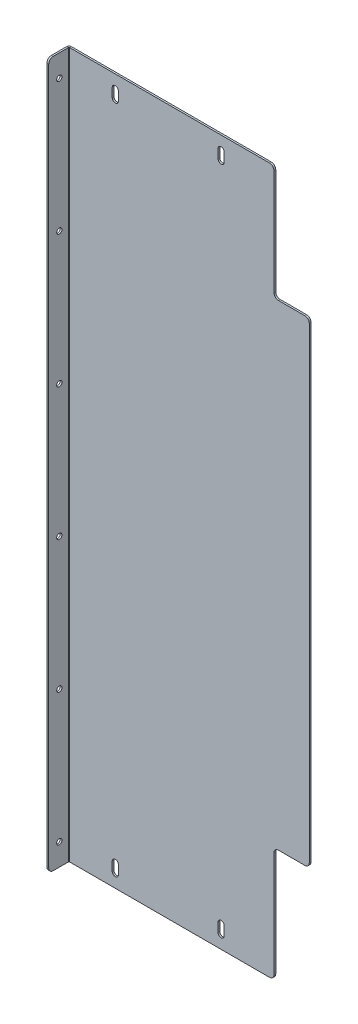
SolidWorks part; units mm, degrees
note: The reader was unsure of these and kept them because the rebuilt part matched: flange length of "边线-法兰1".
ref_plane "前视基准面" through (0, 0, 0) normal (0, 0, 1) x (1, 0, 0)
ref_plane "上视基准面" through (0, 0, 0) normal (0, 1, 0) x (1, 0, 0)
ref_plane "右视基准面" through (0, 0, 0) normal (1, 0, 0) x (0, 0, -1)
sketch "草图1" plane through (0, 0, 0) normal (0, 0, 1) x (1, 0, 0)
  line L1 (275, -400) -> (-275, -400)
  line L2 (275, -400) -> (275, 400)
  line L3 (275, 400) -> (-275, 400)
  line L4 (-275, -400) -> (-275, 400)
  line L5 (275, -400) -> (-275, 400) construction
  line L6 (275, 400) -> (-275, -400) construction
  point P0 (0, 0)
  dimension "D1" = 550
  dimension "D2" = 800
base flange "基体-法兰1" sketch "草图1" thickness 2 reverse thickness direction no parameters "D1"=0.7366
sketch "草图6" plane through (0, 0, 0) normal (0, 0, 1) x (1, 0, 0)
  line L1 (275, 400) -> (235, 400)
  line L2 (275, 400) -> (275, 270)
  line L3 (275, 270) -> (235, 270)
  line L4 (235, 400) -> (235, 270)
  line L5 (275, -400) -> (235, -400)
  line L6 (275, -400) -> (275, -270)
  line L7 (275, -270) -> (235, -270)
  line L8 (235, -400) -> (235, -270)
  dimension "D1" = 40
  dimension "D2" = 40
  dimension "D3" = 130
  dimension "D4" = 130
extrude "切除-拉伸1" cut sketch "草图6" against normal blind 10 normal cut yes
fillet "圆角1" radius 5 8 edges at (235, -270, -1) (235, 270, -1) (-275, -400, -1) (235, -400, -1) (275, -270, -1) (275, 270, -1) (235, 400, -1) (-275, 400, -1)
sketch "草图7" plane through (0, 0, 0) normal (0, 0, 1) x (1, 0, 0)
  line L1 (0.5, -422.7528) -> (-0.5, -422.7528)
  line L2 (0.5, -422.7528) -> (0.5, 422.7528)
  line L3 (0.5, 422.7528) -> (-0.5, 422.7528)
  line L4 (-0.5, -422.7528) -> (-0.5, 422.7528)
  line L5 (0.5, -422.7528) -> (-0.5, 422.7528) construction
  line L6 (0.5, 422.7528) -> (-0.5, -422.7528) construction
  point P0 (0, 0)
  dimension "D1" = 1
extrude "切除-拉伸2" cut sketch "草图7" against normal blind 10 normal cut yes
sketch "草图8" plane through (0, 0, 0) normal (0, 0, 1) x (1, 0, 0)
  line L1 (-0.5, 400) -> (-316.9317, 400)
  line L2 (-0.5, 400) -> (-0.5, -407.8634)
  line L3 (-0.5, -407.8634) -> (-316.9317, -407.8634)
  line L4 (-316.9317, 400) -> (-316.9317, -407.8634)
extrude "切除-拉伸3" cut sketch "草图8" against normal blind 10
edge flange "边线-法兰1" sketch "草图11" flange angle 90 flange length 25 flange position material inside bend radius 0.7366 thickness 2 relief rectangular parameters "D6"=10
sketch "草图11" plane through (0.5, 0, 0) normal (-1, 0, 0) x (0, -1, 0)
  line L2 (-400, 0) -> (-400, 23)
  line L3 (-400, 23) -> (400, 23)
  line L4 (400, 23) -> (400, 0)
  line L7 (400, 0) -> (-400, 0) construction
  line L8 (400, 0) -> (-400, 0)
bend "边线折弯1" bend radius 0.7366 bend angle 90 parameters "D5"=1
fillet "圆角2" radius 5 2 edges at (1.5, 400, 23) (1.5, -400, 23)
sketch "草图12" plane through (0, 0, 0) normal (0, 0, 1) x (1, 0, 0)
  line L0 (55, 375) -> (55, 385) construction
  line L1 (51.5, 375) -> (51.5, 385)
  line L2 (58.5, 375) -> (58.5, 385)
  line L3 (175, 375) -> (175, 385) construction
  line L4 (171.5, 375) -> (171.5, 385)
  line L5 (178.5, 375) -> (178.5, 385)
  line L6 (55, -385) -> (55, -375) construction
  line L7 (51.5, -385) -> (51.5, -375)
  line L8 (58.5, -385) -> (58.5, -375)
  line L9 (175, -385) -> (175, -375) construction
  line L10 (171.5, -385) -> (171.5, -375)
  line L11 (178.5, -385) -> (178.5, -375)
  line L12 (235, 395) -> (235, 275) construction
  arc A0 (51.5, 375) -> (58.5, 375) centre (55, 375) ccw
  arc A1 (58.5, 385) -> (51.5, 385) centre (55, 385) ccw
  arc A2 (171.5, 375) -> (178.5, 375) centre (175, 375) ccw
  arc A3 (178.5, 385) -> (171.5, 385) centre (175, 385) ccw
  arc A4 (51.5, -385) -> (58.5, -385) centre (55, -385) ccw
  arc A5 (58.5, -375) -> (51.5, -375) centre (55, -375) ccw
  arc A6 (171.5, -385) -> (178.5, -385) centre (175, -385) ccw
  arc A7 (178.5, -375) -> (171.5, -375) centre (175, -375) ccw
  point P2 (55, 380)
  point P8 (175, 380)
  point P15 (55, -380)
  point P22 (175, -380)
  dimension "D12" = 120
  dimension "D1" = 7
  dimension "D2" = 7
  dimension "D3" = 10
  dimension "D4" = 10
  dimension "D5" = 7
  dimension "D6" = 7
  dimension "D7" = 760
  dimension "D8" = 380
  dimension "D9" = 10
  dimension "D10" = 10
  dimension "D11" = 60
extrude "切除-拉伸4" cut sketch "草图12" against normal blind 10 normal cut yes
sketch "草图13" plane through (2.5, 0, 0) normal (1, 0, 0) x (0, 0, -1)
  line L0 (-0.7366, -400) -> (-18, -400) construction
  line L1 (-23, -395) -> (-23, 395) construction
  circle A0 centre (-11, -375) radius 3
  dimension "D3" = 6
  dimension "D1" = 25
  dimension "D2" = 12
extrude "切除-拉伸5" cut sketch "草图13" against normal blind 10 normal cut yes
pattern_linear "阵列(线性)1" count 6 spacing 150 along (0, 1, 0) of "切除-拉伸5"
sketch "折弯-线1" [suppressed] plane through (0, 0, 0) normal (0, 1, 0) x (1, 0, 0)
sketch "边界框1" [suppressed] plane through (0, 0, 0) normal (0, 1, 0) x (1, 0, 0)
sheet metal parameters "钣金1" thickness 2 parameters "D1"=0.7366
flat pattern "平板型式1" [suppressed]
sketch "折弯-线2" plane through (0, 0, 0) normal (0, 1, 0) x (1, 0, 0)
sketch3d "边界框2" [suppressed]
  line L0 (275, 310, 0) -> (275, -310, 0) construction
  line L1 (-275, 310, 0) -> (-275, -310, 0) construction
  line L2 (275, 310, 0) -> (-275, 310, 0) construction
  line L3 (275, -310, 0) -> (-275, -310, 0) construction
sheet metal parameters "钣金2" thickness 2 parameters "D1"=0.7366
flat pattern "平板型式1"
sketch "折弯-线2" plane through (0, 0, 0) normal (0, 1, 0) x (1, 0, 0)
sketch3d "边界框2" [suppressed]
  line L0 (275, -400, 0) -> (275, 400, 0) construction
  line L1 (-275, -400, 0) -> (-275, 400, 0) construction
  line L2 (275, -400, 0) -> (-275, -400, 0) construction
  line L3 (275, 400, 0) -> (-275, 400, 0) construction
sheet metal parameters "钣金3" thickness 2 parameters "D1"=0.7366
flat pattern "平板型式3"
sketch "折弯-线3" plane through (0, 0, 0) normal (0, 1, 0) x (1, 0, 0)
sketch3d "边界框3" [suppressed]
  line L0 (-0.5, -400, 0) -> (-0.5, 400, 0) construction
  line L1 (-275, -400, 0) -> (-275, 400, 0) construction
  line L2 (-0.5, -400, 0) -> (-275, -400, 0) construction
  line L3 (-0.5, 400, 0) -> (-275, 400, 0) construction
sheet metal parameters "钣金4" thickness 2 parameters "D1"=0.7366
flat pattern "平板型式4"
sketch "折弯-线4" plane through (0, 0, 0) normal (0, 1, 0) x (1, 0, 0)
sketch3d "边界框4" [suppressed]
  line L0 (274.9999, -400, 0) -> (275, 400, 0) construction
  line L1 (0.5, -400, 0) -> (0.5001, 400, 0) construction
  line L2 (274.9999, -400, 0) -> (0.5, -400, 0) construction
  line L3 (275, 400, 0) -> (0.5001, 400, 0) construction
sheet metal parameters "钣金5" thickness 2 parameters "D1"=0.7366
flat pattern "平板型式4"
sketch "折弯-线4" plane through (0, 0, 0) normal (0, 0, 1) x (1, 0, 0)
  line L0 (1.8727, 400) -> (1.8727, -400) construction
  line L1 (1.8727, 400) -> (1.8727, -400) construction
sketch3d "边界框4" [suppressed]
  line L0 (274.9999, -400, 0) -> (275, 400, 0) construction
  line L1 (-21.7546, -400, 0) -> (-21.7546, 400, 0) construction
  line L2 (274.9999, -400, 0) -> (-21.7546, -400, 0) construction
  line L3 (275, 400, 0) -> (-21.7546, 400, 0) construction
bend of the flat pattern "展平-<边线折弯1>1"
sheet metal parameters "钣金6" thickness 2 parameters "D1"=0.7366
flat pattern "平板型式4"
sketch "折弯-线4" plane through (0, 0, 0) normal (0, 0, 1) x (1, 0, 0)
  line L0 (1.8727, 400) -> (1.8727, -400) construction
  line L1 (1.8727, 400) -> (1.8727, -400) construction
sketch3d "边界框4" [suppressed]
  line L0 (274.9999, -400, 0) -> (275, 400, 0) construction
  line L1 (-21.7546, -400, 0) -> (-21.7546, 400, 0) construction
  line L2 (274.9999, -400, 0) -> (-21.7546, -400, 0) construction
  line L3 (275, 400, 0) -> (-21.7546, 400, 0) construction
bend of the flat pattern "展平-<边线折弯1>1"
sheet metal parameters "钣金7" thickness 2 parameters "D1"=0.7366
flat pattern "平板型式4"
sketch "折弯-线4" plane through (0, 0, 0) normal (0, 0, 1) x (1, 0, 0)
  line L0 (1.8727, 400) -> (1.8727, -400) construction
  line L1 (1.8727, 400) -> (1.8727, -400) construction
sketch3d "边界框4" [suppressed]
  line L0 (274.9999, -400, 0) -> (275, 400, 0) construction
  line L1 (-21.7546, -400, 0) -> (-21.7546, 400, 0) construction
  line L2 (274.9999, -400, 0) -> (-21.7546, -400, 0) construction
  line L3 (275, 400, 0) -> (-21.7546, 400, 0) construction
bend of the flat pattern "展平-<边线折弯1>1"
sheet metal parameters "钣金8" thickness 2 parameters "D1"=0.7366
flat pattern "平板型式4"
sketch "折弯-线4" plane through (0, 0, 0) normal (0, 0, 1) x (1, 0, 0)
  line L0 (1.8727, 400) -> (1.8727, -400) construction
  line L1 (1.8727, 400) -> (1.8727, -400) construction
sketch3d "边界框4" [suppressed]
  line L0 (274.9999, -400, 0) -> (275, 400, 0) construction
  line L1 (-21.7546, -400, 0) -> (-21.7546, 400, 0) construction
  line L2 (274.9999, -400, 0) -> (-21.7546, -400, 0) construction
  line L3 (275, 400, 0) -> (-21.7546, 400, 0) construction
bend of the flat pattern "展平-<边线折弯1>1"
